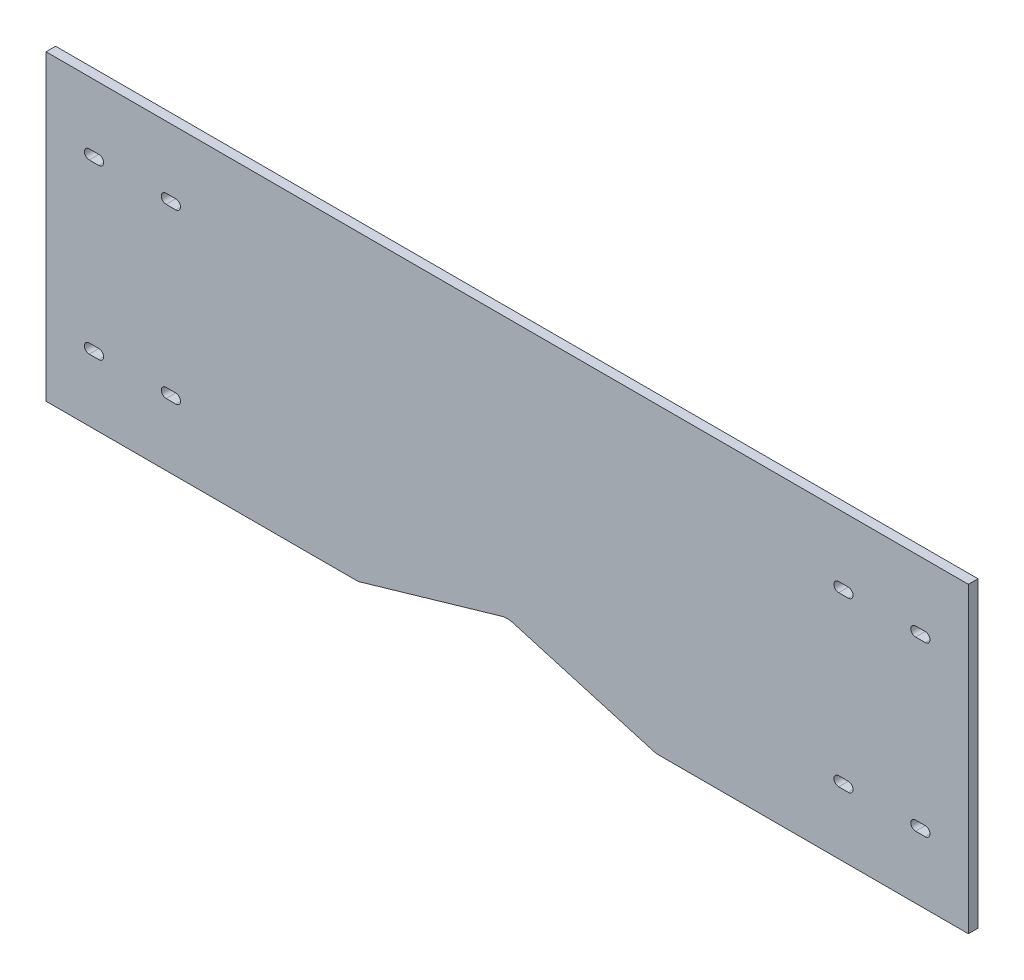
SolidWorks part; units mm, degrees
material "PC High Viscosity"
ref_plane "Front Plane" through (0, 0, 0) normal (0, 0, 1) x (1, 0, 0)
ref_plane "Top Plane" through (0, 0, 0) normal (0, 1, 0) x (1, 0, 0)
ref_plane "Right Plane" through (0, 0, 0) normal (1, 0, 0) x (0, 0, -1)
sketch "Sketch1" plane through (0, 0, 0) normal (0, 0, 1) x (1, 0, 0)
  line L1 (-304.8, -100.0125) -> (304.8, -100.0125)
  line L2 (-304.8, -100.0125) -> (-304.8, 100.0125)
  line L3 (-304.8, 100.0125) -> (304.8, 100.0125)
  line L4 (304.8, -100.0125) -> (304.8, 100.0125)
  line L5 (-304.8, -100.0125) -> (304.8, 100.0125) construction
  line L6 (-304.8, 100.0125) -> (304.8, -100.0125) construction
  point P0 (0, 0)
  dimension "D1" = 200.025
  dimension "D2" = 609.6
extrude "Boss-Extrude1" add sketch "Sketch1" along normal blind 6.35
hole_wizard "1/4 (0.25) Diameter Slot1" positions "Sketch2" profile "Sketch3" size "1/4" standard "ANSI Inch" slot yes end condition through all
sketch "Sketch2" plane through (0, 0, 6.35) normal (0, 0, 1) x (1, 0, 0)
  line L0 (-273.05, 100.0125) -> (-273.05, -100.0125) construction
  line L1 (304.8, 100.0125) -> (-304.8, 100.0125) construction
  line L2 (-304.8, -100.0125) -> (304.8, -100.0125) construction
  line L4 (273.05, 100.0125) -> (273.05, -100.0125) construction
  line L7 (0, 100.0125) -> (0, -100.0125) construction
  line L9 (-279.4, 55.5625) -> (-266.7, 55.5625) construction
  point P14 (-273.05, 55.5625)
  point P16 (-273.05, -55.5625)
  point P18 (273.05, -55.5625)
  point P20 (273.05, 55.5625)
  point P29 (-222.25, 55.5625)
  point P31 (-222.25, -55.5625)
  point P33 (222.25, 55.5625)
  point P35 (222.25, -55.5625)
  point P48 (-266.7, 55.5625)
  dimension "D1" = 44.45
  dimension "D3" = 44.45
  dimension "D5" = 44.45
  dimension "D6" = 44.45
  dimension "D7" = 50.8
  dimension "D8" = 50.8
  dimension "D2" = 546.1
  dimension "D4" = 273.05
  dimension "D9" = 12.7
sketch "Sketch3" plane through (222.25, -55.5625, 6.35) normal (1, 0, 0) x (0, -1, 0)
  line L0 (0, 0) -> (0, 6.35)
  line L1 (0, 6.35) -> (3.175, 6.35)
  line L2 (3.175, 6.35) -> (3.175, 0)
  line L5 (3.175, 0) -> (0, 0)
  line L11 (0, -6.35) -> (0, 107.95) construction
  dimension "Thru Hole Dia." = 6.35
  dimension "Thru Hole Depth" = 6.35
sketch "Sketch4" plane through (0, 0, 6.35) normal (0, 0, 1) x (1, 0, 0)
  line L0 (0, 100.0125) -> (0, -100.0125) construction
  line L1 (304.8, 100.0125) -> (-304.8, 100.0125) construction
  line L2 (-304.8, -100.0125) -> (304.8, -100.0125) construction
  line L3 (-98.425, -100.0125) -> (0, -71.4375) construction
  line L4 (0, -71.4375) -> (98.425, -100.0125) construction
  line L5 (-98.425, -100.0125) -> (-3.5409, -72.4655)
  line L6 (3.5409, -72.4655) -> (98.425, -100.0125)
  line L7 (98.425, -100.0125) -> (-98.425, -100.0125)
  arc A0 (-3.5409, -72.4655) -> (3.5409, -72.4655) centre (0, -84.6619) cw
  dimension "D3" = 12.7
  dimension "D1" = 196.85
  dimension "D2" = 28.575
extrude "Cut-Extrude1" cut sketch "Sketch4" against normal through all
equation "\"D4@Sketch2\"=\"D2@Sketch2\"/2"
